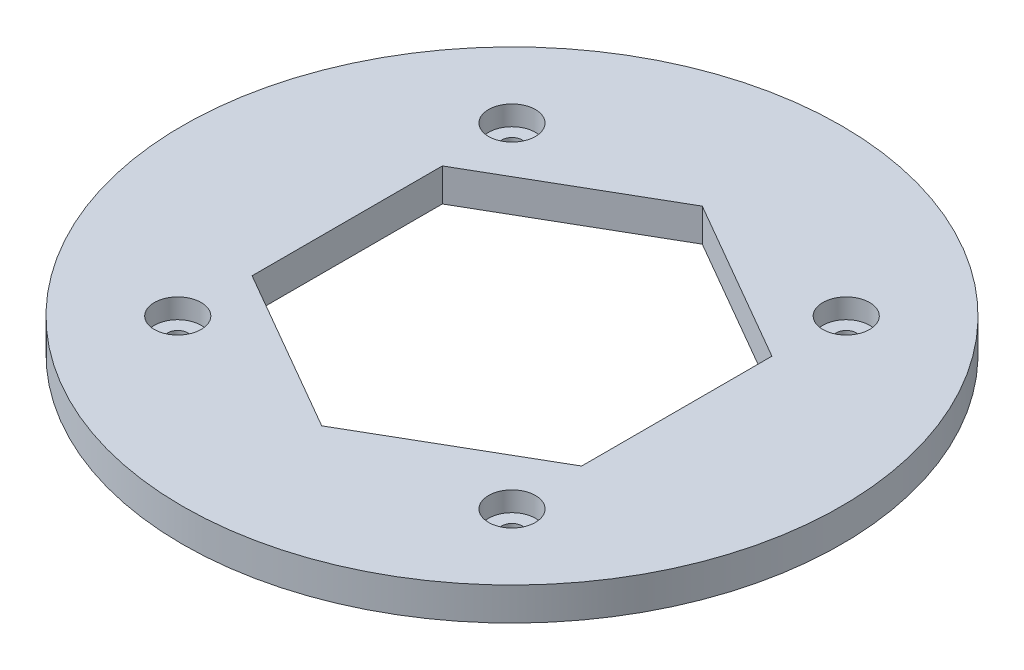
SolidWorks part; units mm, degrees
ref_plane "Front Plane" through (0, 0, 0) normal (0, 0, 1) x (1, 0, 0)
ref_plane "Top Plane" through (0, 0, 0) normal (0, 1, 0) x (1, 0, 0)
ref_plane "Right Plane" through (0, 0, 0) normal (1, 0, 0) x (0, 0, -1)
sketch "Sketch1" plane through (0, 0, 0) normal (0, 1, 0) x (1, 0, 0)
  line L0 (-25.3553, -25.3553) -> (-25.3553, 25.3553) construction
  line L1 (-35.3553, -35.3553) -> (35.3553, -35.3553) construction
  line L2 (-35.3553, -35.3553) -> (-35.3553, 35.3553) construction
  line L3 (-35.3553, 35.3553) -> (35.3553, 35.3553) construction
  line L4 (35.3553, -35.3553) -> (35.3553, 35.3553) construction
  line L5 (-35.3553, -35.3553) -> (35.3553, 35.3553) construction
  line L6 (-35.3553, 35.3553) -> (35.3553, -35.3553) construction
  line L7 (-25.3553, 25.3553) -> (25.3553, 25.3553) construction
  line L8 (25.3553, -25.3553) -> (25.3553, 25.3553) construction
  line L9 (-25.3553, -25.3553) -> (25.3553, -25.3553) construction
  line L10 (0, -55) -> (0, 55) construction
  line L11 (-55, 0) -> (55, 0) construction
  circle A0 centre (0, 0) radius 50
  circle A1 centre (-25.3553, 25.3553) radius 1.55
  circle A2 centre (-25.3553, 25.3553) radius 3.55
  circle A3 centre (25.3553, 25.3553) radius 1.55
  circle A4 centre (25.3553, 25.3553) radius 3.55
  circle A5 centre (-25.3553, -25.3553) radius 3.55
  circle A6 centre (-25.3553, -25.3553) radius 1.55
  circle A7 centre (25.3553, -25.3553) radius 1.55
  circle A8 centre (25.3553, -25.3553) radius 3.55
  dimension "D1" = 100
  dimension "D3" = 2
  dimension "D4" = 3.1
  dimension "D2" = 10
extrude "Boss-Extrude1" add sketch "Sketch1" along normal blind 5 contours A0 A8 A4 A2 A5 region at (0, 0, 0)
extrude "Boss-Extrude2" add sketch "Sketch1<3>" along normal blind 2 contours A8 A7 | A4 A3 | A2 A1 | A5 A6 region at (-28.8049, 0, -25.3553) region at (21.9057, 0, -25.3553) region at (-28.8049, 0, 25.3553) region at (21.9057, 0, 25.3553)
sketch "Sketch1<3>" plane through (0, 0, 0) normal (0, 1, 0) x (1, 0, 0) same geometry as "Sketch1"
sketch "Sketch2" plane through (0, 0, 0) normal (0, -1, 0) x (1, 0, 0)
  line L1 (-35.3553, -35.3553) -> (35.3553, -35.3553) construction
  line L2 (-35.3553, -35.3553) -> (-35.3553, 35.3553) construction
  line L3 (-35.3553, 35.3553) -> (35.3553, 35.3553) construction
  line L4 (35.3553, -35.3553) -> (35.3553, 35.3553) construction
  line L5 (-35.3553, -35.3553) -> (35.3553, 35.3553) construction
  line L6 (-35.3553, 35.3553) -> (35.3553, -35.3553) construction
  circle A0 centre (0, 0) radius 50 construction
  circle A1 centre (0, 35.3553) radius 5.5
  point P0 (0, 0)
extrude "Cut-Extrude1" cut sketch "Sketch2" against normal blind 2.5
sketch "Sketch3" plane through (0, 5, 0) normal (0, 1, 0) x (1, 0, 0)
  line L1 (0, 28.8675) -> (-25, 14.4338)
  line L2 (-25, 14.4338) -> (-25, -14.4338)
  line L3 (-25, -14.4338) -> (0, -28.8675)
  line L4 (0, -28.8675) -> (25, -14.4338)
  line L5 (25, -14.4338) -> (25, 14.4338)
  line L6 (25, 14.4338) -> (0, 28.8675)
  circle A0 centre (0, 0) radius 25 construction
  dimension "D1" = 50
extrude "Cut-Extrude2" cut sketch "Sketch3" against normal blind 10
